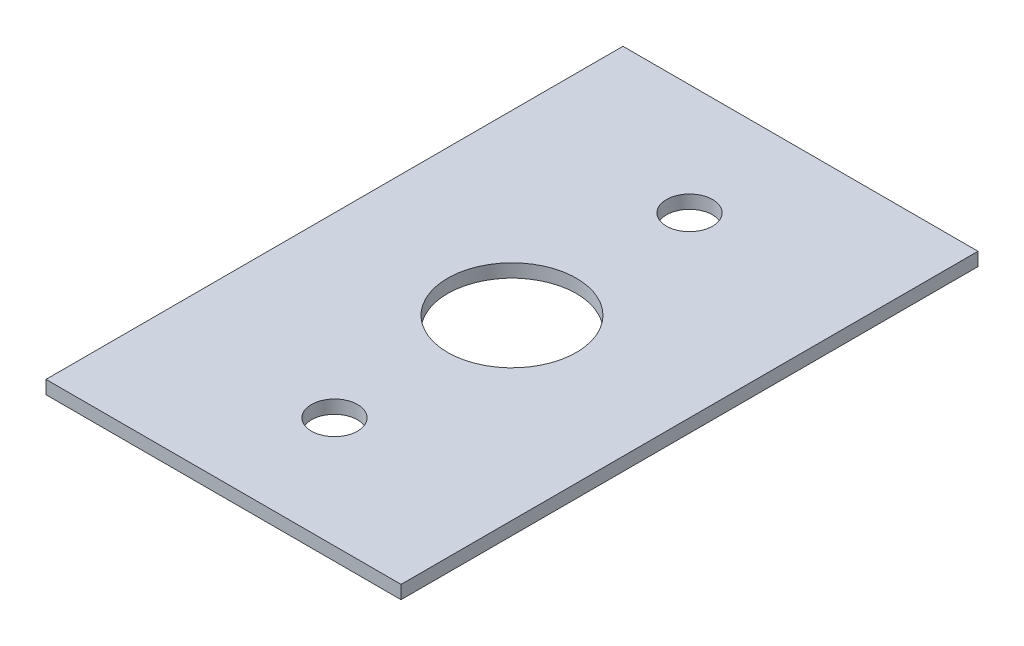
SolidWorks part; units mm, degrees
material "1.0037 (S235JR)"
ref_plane "Plan de face" through (0, 0, 0) normal (0, 0, 1) x (1, 0, 0)
ref_plane "Plan de dessus" through (0, 0, 0) normal (0, 1, 0) x (1, 0, 0)
ref_plane "Plan de droite" through (0, 0, 0) normal (1, 0, 0) x (0, 0, -1)
sketch "Esquisse1" plane through (0, 0, 0) normal (0, 1, 0) x (1, 0, 0)
  line L1 (20, 32.5) -> (-20, 32.5)
  line L2 (20, 32.5) -> (20, -32.5)
  line L3 (20, -32.5) -> (-20, -32.5)
  line L4 (-20, 32.5) -> (-20, -32.5)
  line L5 (20, 32.5) -> (-20, -32.5) construction
  line L6 (20, -32.5) -> (-20, 32.5) construction
  point P0 (0, 0)
  dimension "D1" = 65
  dimension "D2" = 40
base flange "Tôle de base pliée1" sketch "Esquisse1" thickness 1.5 reverse thickness direction no parameters "D1"=0.7366
sketch "Esquisse6" plane through (0, 0, 0) normal (0, 1, 0) x (1, 0, 0)
  line L5 (20, 32.5) -> (-20, 32.5) construction
  line L6 (-0.825, 0) -> (0.825, 0) construction
  circle A0 centre (0, 20) radius 2.6
  circle A4 centre (0, -20) radius 2.6
  point P0 (0, 0)
  point P1 (0, 0)
  point P4 (0, 0)
  point P8 (0, 32.5)
  point P10 (-26.1207, 26.1207)
  dimension "D4" = 5.2
  dimension "D1" = 12.5
extrude "Passage_Vis_M5" cut sketch "Esquisse6" against normal up to next normal cut yes
sketch "Esquisse7" plane through (0, 0, 0) normal (0, 1, 0) x (1, 0, 0)
  circle A0 centre (0, 0) radius 7.25
  dimension "D1" = 14.5
extrude "Passage_Jauge" cut sketch "Esquisse7" against normal up to next normal cut yes
sketch "Lignes de pliage1" [suppressed] plane through (0, 0, 0) normal (0, 1, 0) x (1, 0, 0)
sketch "Cube de visualisation1" [suppressed] plane through (0, 0, 0) normal (0, 1, 0) x (1, 0, 0)
sheet metal parameters "Tôlerie1" thickness 1.5 parameters "D1"=0.7366
flat pattern "Etat déplié1" [suppressed]
sketch "Lignes de pliage2" plane through (0, 0, 0) normal (0, 1, 0) x (1, 0, 0)
sketch3d "Cube de visualisation2" [suppressed]
  line L0 (27.5, -27.5, 0) -> (27.5, 27.5, 0) construction
  line L1 (-27.5, -27.5, 0) -> (-27.5, 27.5, 0) construction
  line L2 (27.5, -27.5, 0) -> (-27.5, -27.5, 0) construction
  line L3 (27.5, 27.5, 0) -> (-27.5, 27.5, 0) construction
sheet metal parameters "Tôlerie2" thickness 1.5 parameters "D1"=0.7366
flat pattern "Etat déplié1"
sketch "Lignes de pliage2" plane through (0, 0, 0) normal (0, 1, 0) x (1, 0, 0)
sketch3d "Cube de visualisation2" [suppressed]
  line L0 (-27.5, -27.5, 0) -> (-27.5, 27.5, 0) construction
  line L1 (27.5, -27.5, 0) -> (27.5, 27.5, 0) construction
  line L2 (-27.5, -27.5, 0) -> (27.5, -27.5, 0) construction
  line L3 (-27.5, 27.5, 0) -> (27.5, 27.5, 0) construction
sheet metal parameters "Tôlerie4" thickness 1.5 parameters "D1"=0.7366
flat pattern "Etat déplié1"
sketch "Lignes de pliage2" plane through (0, 0, 0) normal (0, 1, 0) x (1, 0, 0)
sketch3d "Cube de visualisation2" [suppressed]
  line L0 (-20, -32.5, 0) -> (-20, 32.5, 0) construction
  line L1 (20, -32.5, 0) -> (20, 32.5, 0) construction
  line L2 (-20, -32.5, 0) -> (20, -32.5, 0) construction
  line L3 (-20, 32.5, 0) -> (20, 32.5, 0) construction
